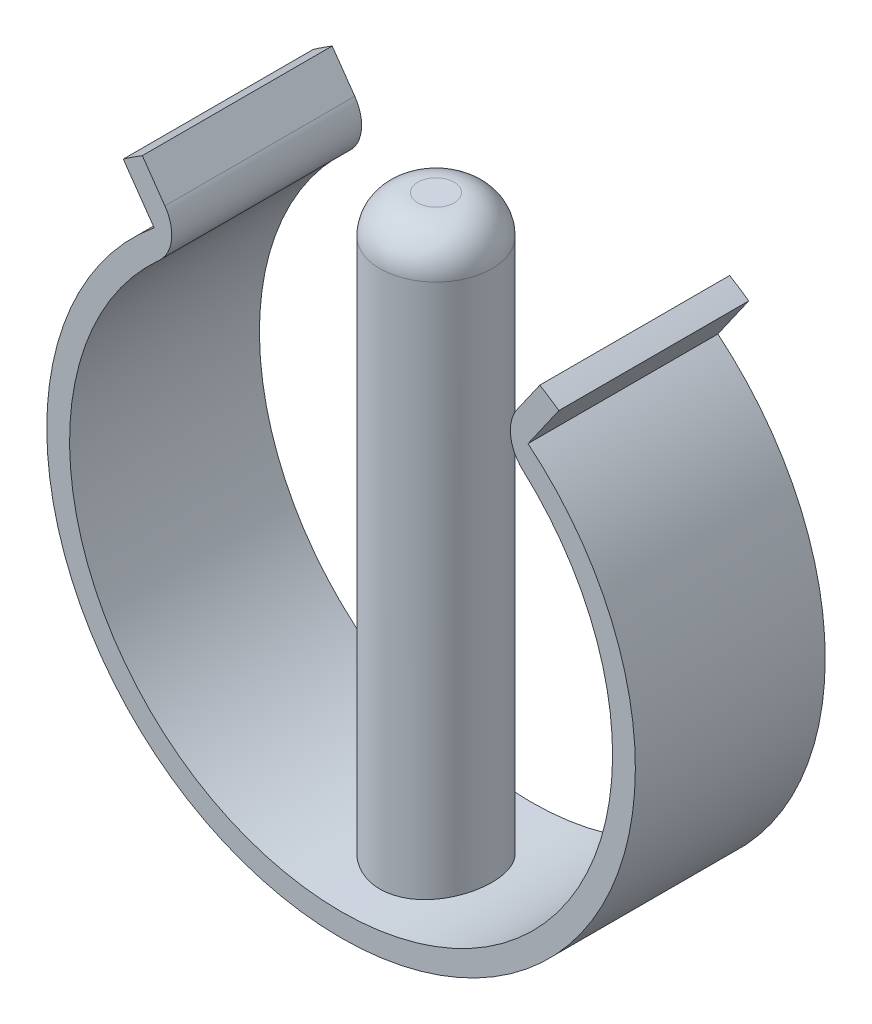
SolidWorks part; units mm, degrees
ref_plane "Front Plane" through (0, 0, 0) normal (0, 0, 1) x (1, 0, 0)
ref_plane "Top Plane" through (0, 0, 0) normal (0, 1, 0) x (1, 0, 0)
ref_plane "Right Plane" through (0, 0, 0) normal (1, 0, 0) x (0, 0, -1)
sketch "Sketch1" plane through (0, 0, 0) normal (0, 0, 1) x (1, 0, 0)
  line L0 (0, 0) -> (0, 22.5545) construction
  line L1 (8.2021, 11.7139) -> (10.4679, 14.9497)
  line L2 (-8.2021, 11.7139) -> (-10.4679, 14.9497)
  line L3 (-9.8467, 11.9705) -> (-11.4715, 14.2909)
  line L4 (9.8467, 11.9705) -> (11.4715, 14.2909)
  line L5 (0, -2.0921) -> (-16.6194, 21.6428) construction
  line L6 (0, 0) -> (-15.6364, 22.331) construction
  line L7 (0, 0) -> (15.459, 22.0778) construction
  line L8 (0, -2.0921) -> (16.442, 21.3895) construction
  arc A0 (-8.2021, 11.7139) -> (8.2021, 11.7139) centre (0, 0) ccw
  arc A1 (-9.8467, 11.9705) -> (9.8467, 11.9705) centre (0, 0) ccw
  arc A2 (11.4715, 14.2909) -> (10.4679, 14.9497) centre (0, -2.0921) ccw
  arc A3 (-10.4679, 14.9497) -> (-11.4715, 14.2909) centre (0, -2.0921) ccw
  circle A4 centre (0, 0) radius 15.5 construction
  circle A5 centre (0, 0) radius 14.3 construction
  dimension "D1" = 1.2
  dimension "D2" = 35
  dimension "D3" = 35
  dimension "D4" = 1.2
extrude "Boss-Extrude1" add sketch "Sketch1" along normal blind 5 and the other way blind 5
sketch "Sketch2" plane through (0, 0, 0) normal (0, 1, 0) x (1, 0, 0)
  circle A0 centre (0, 0) radius 2.95
  dimension "D1" = 5.9
extrude "Boss-Extrude2" add sketch "Sketch2" along normal blind 16 and the other way up to next
fillet "Fillet2" radius 2 1 edges at (0, 16, 2.95)
fillet "Fillet3" radius 2 2 edges at (8.2021, 11.7139, 0) (-8.2021, 11.7139, 0)
sketch "Sketch4" plane through (0, 0, 0) normal (1, 0, 0) x (0, 0, -1)
  line L0 (5, -14.9862) -> (-5, -14.9862) construction
  line L1 (5, -15.5) -> (5, 11.9705) construction
  line L2 (-5, 11.9705) -> (-5, -15.5) construction
  line L3 (0, -14.9862) -> (0, -9.6925) construction
  line L4 (0, -14.9862) -> (-4.6963, -14.9862)
  line L5 (0, -14.9862) -> (0, -16.2366)
  arc A0 (0, -16.2366) -> (-4.6963, -14.9862) centre (-0.3715, -8.1872) cw
  point P12 (-3.9919, -15.3861)
  point P13 (0, 0)
  point P14 (0, 0)
  point P15 (0, 0)
  point P16 (0, 0)
revolve "Revolve1" add sketch "Sketch4" angle 360 about L3
